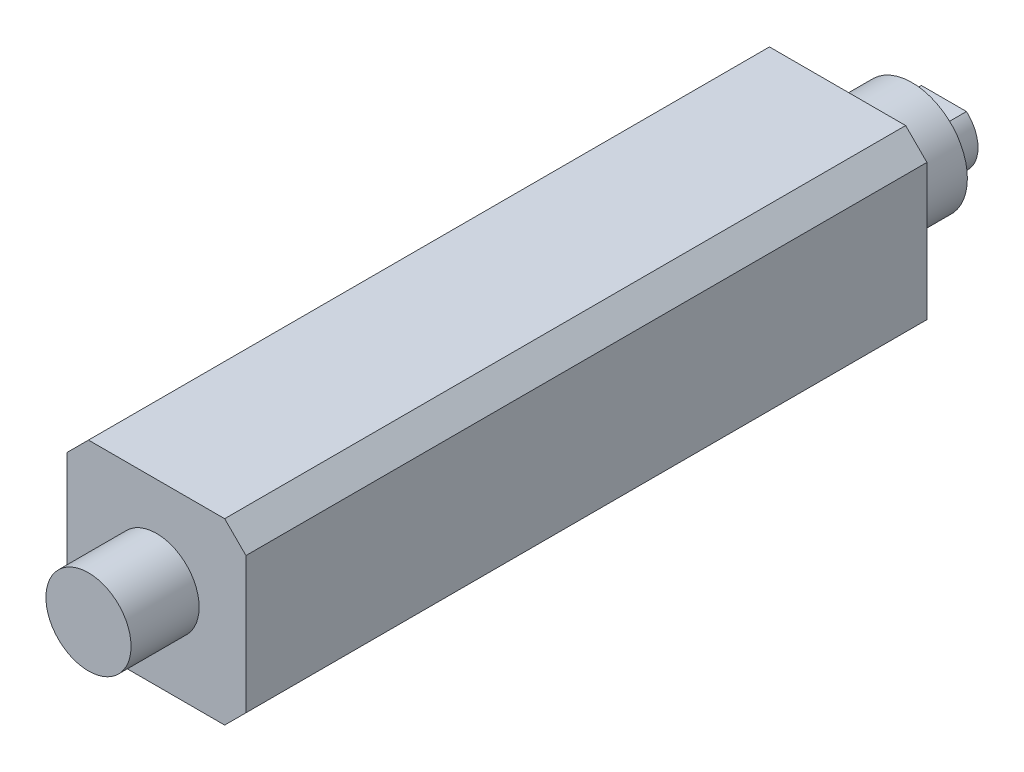
SolidWorks part; units mm, degrees
ref_plane "정면" through (0, 0, 0) normal (0, 0, 1) x (1, 0, 0)
ref_plane "윗면" through (0, 0, 0) normal (0, 1, 0) x (1, 0, 0)
ref_plane "우측면" through (0, 0, 0) normal (1, 0, 0) x (0, 0, -1)
sketch "스케치1" plane through (0, 0, 0) normal (0, 0, 1) x (1, 0, 0)
  line L0 (-21, 16) -> (-16, 21)
  line L1 (-16, -21) -> (16, -21)
  line L2 (-21, -16) -> (-21, 16)
  line L3 (-16, 21) -> (16, 21)
  line L4 (21, -16) -> (21, 16)
  line L5 (-21, -21) -> (21, 21) construction
  line L6 (-21, 21) -> (21, -21) construction
  line L7 (16, 21) -> (21, 16)
  line L8 (-21, -16) -> (-16, -21)
  line L9 (16, -21) -> (21, -16)
  point P0 (0, 0)
  dimension "D1" = 42
  dimension "D2" = 42
extrude "보스-돌출1" add sketch "스케치1" along normal blind 160
sketch "스케치2" plane through (0, 0, 0) normal (0, 0, 1) x (1, 0, 0)
  circle A0 centre (0, 0) radius 15
  dimension "D1" = 30
extrude "보스-돌출2" add sketch "스케치2" against normal blind 3
sketch "스케치3" plane through (0, 0, -3) normal (0, 0, -1) x (-1, 0, 0)
  circle A0 centre (0, 0) radius 13
  dimension "D1" = 26
extrude "보스-돌출3" add sketch "스케치3" along normal blind 14.5
sketch "스케치4" plane through (0, 0, -17.5) normal (0, 0, -1) x (-1, 0, 0)
  circle A0 centre (0, 0) radius 8
  dimension "D1" = 16
extrude "보스-돌출4" add sketch "스케치4" along normal blind 7.5
sketch "스케치5" plane through (0, 0, 160) normal (0, 0, 1) x (1, 0, 0)
  circle A0 centre (0, 0) radius 10
  dimension "D1" = 20
extrude "보스-돌출5" add sketch "스케치5" along normal blind 16
sketch "스케치6" plane through (0, 0, -25) normal (0, 0, -1) x (-1, 0, 0)
  line L0 (-5.2915, 6) -> (5.2915, 6)
  line L1 (-5.2915, -6) -> (5.2915, -6)
  arc A0 (-5.2915, -6) -> (5.2915, -6) centre (0, 0) ccw
  arc A1 (5.2915, 6) -> (-5.2915, 6) centre (0, 0) ccw
  point P7 (0, 0)
  dimension "D1" = 16
  dimension "D2" = 12
extrude "컷-돌출1" cut sketch "스케치6" against normal blind 5
hole_wizard "M10x1.25 탭을 위한 탭 드릴1" positions "스케치8" profile "스케치9" hole size "M10x1.25" standard "ISO"
sketch "스케치8" plane through (0, 0, -25) normal (0, 0, -1) x (-1, 0, 0)
  point P0 (0, 0)
sketch "스케치9" plane through (0, 0, -25) normal (1, 0, 0) x (0, 1, 0)
  line L0 (0, 0) -> (0, 17.6438)
  line L1 (0, 17.6438) -> (4.4, 15)
  line L2 (4.4, 15) -> (4.4, 0)
  line L5 (4.4, 0) -> (0, 0)
  line L10 (0, 17.6438) -> (-4.4, 15) construction
  line L11 (0, -6.35) -> (0, 107.95) construction
  dimension "구멍 지름" = 8.8
  dimension "구멍 깊이" = 15
  dimension "드릴 각도" = 118
